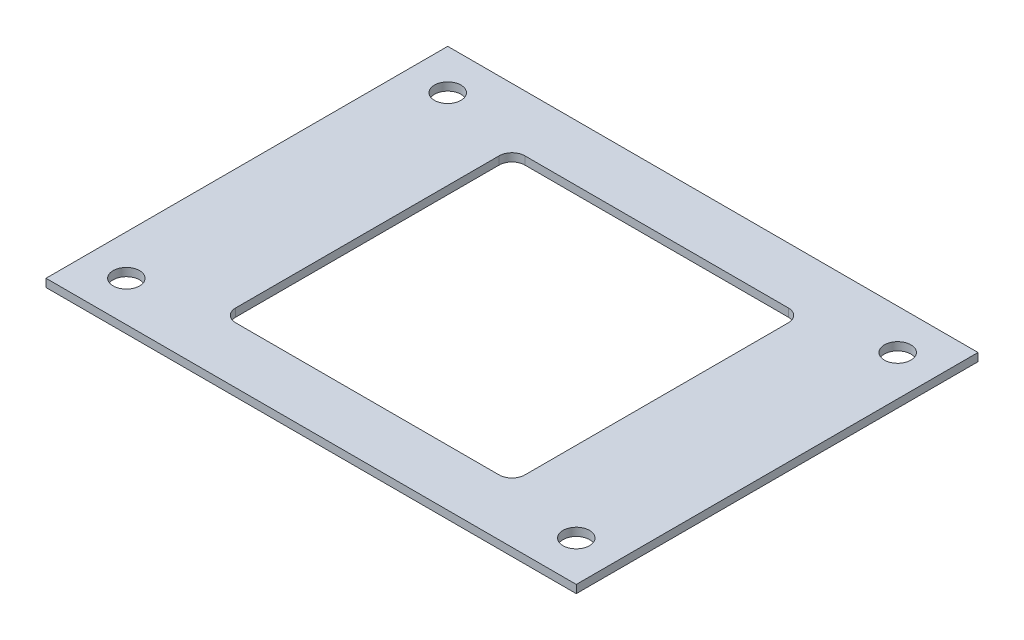
SolidWorks part; units mm, degrees
ref_plane "Front Plane" through (0, 0, 0) normal (0, 0, 1) x (1, 0, 0)
ref_plane "Top Plane" through (0, 0, 0) normal (0, 1, 0) x (1, 0, 0)
ref_plane "Right Plane" through (0, 0, 0) normal (1, 0, 0) x (0, 0, -1)
sketch "Sketch1" plane through (0, 0, 0) normal (0, 1, 0) x (1, 0, 0)
  line L1 (-33, -25) -> (33, -25)
  line L2 (-33, -25) -> (-33, 25)
  line L3 (-33, 25) -> (33, 25)
  line L4 (33, -25) -> (33, 25)
  line L5 (-33, -25) -> (33, 25) construction
  line L6 (-33, 25) -> (33, -25) construction
  line L7 (-18, -18) -> (18, -18)
  line L8 (-18, -18) -> (-18, 18)
  line L9 (-18, 18) -> (18, 18)
  line L10 (18, -18) -> (18, 18)
  line L11 (-18, -18) -> (18, 18) construction
  line L12 (-18, 18) -> (18, -18) construction
  circle A0 centre (-28, 20) radius 1.65
  circle A1 centre (-28, -20) radius 1.65
  circle A2 centre (28, 20) radius 1.65
  circle A3 centre (28, -20) radius 1.65
  point P0 (0, 0)
  point P5 (0, 0)
  dimension "D5" = 2
  dimension "D6" = 2
  dimension "D7" = 10
  dimension "D8" = 10
  dimension "D9" = 3.3
  dimension "D10" = 3.3
  dimension "D11" = 2
  dimension "D12" = 2
  dimension "D13" = 10
  dimension "D15" = 3.3
  dimension "D16" = 3.3
  dimension "D1" = 66
  dimension "D2" = 50
  dimension "D3" = 36
  dimension "D4" = 36
  dimension "D14" = 10
extrude "Boss-Extrude1" add sketch "Sketch1" along normal blind 1
fillet "Fillet1" radius 1.6 4 edges at (-18, 0.5, 18) (18, 0.5, 18) (18, 0.5, -18) (-18, 0.5, -18)
